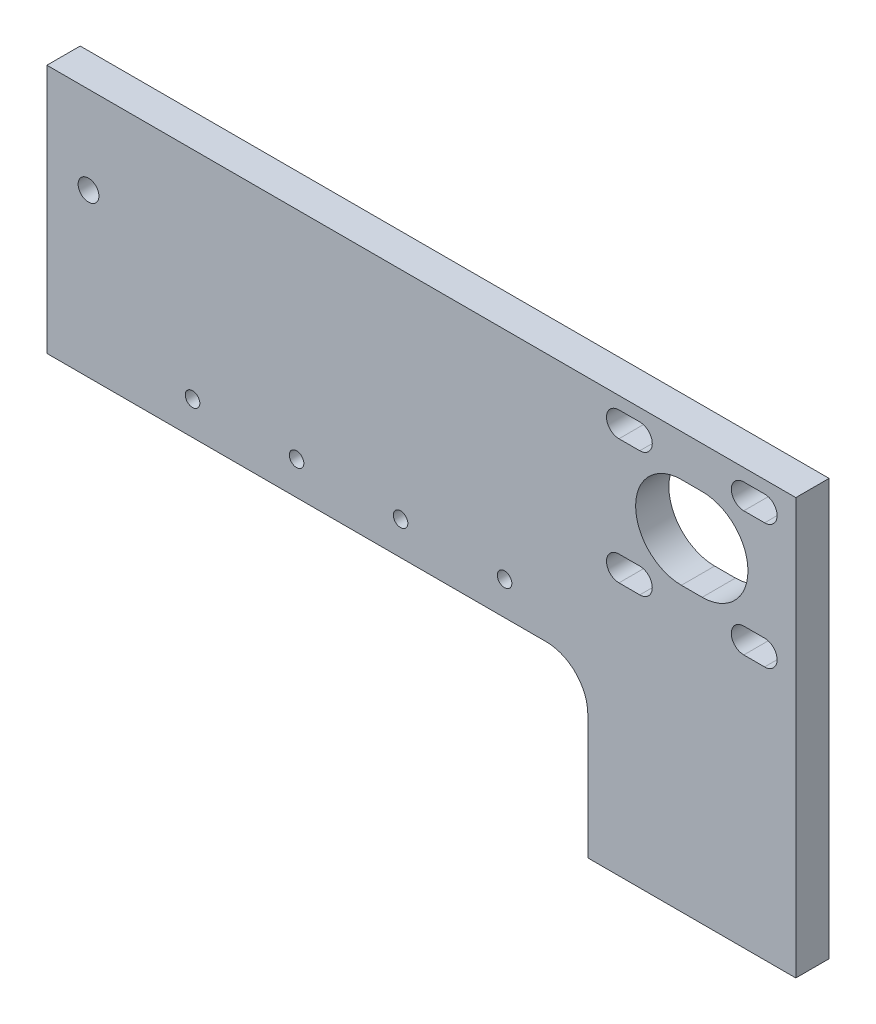
SolidWorks part; units mm, degrees
ref_plane "Front Plane" through (0, 0, 0) normal (0, 0, 1) x (1, 0, 0)
ref_plane "Top Plane" through (0, 0, 0) normal (0, 1, 0) x (1, 0, 0)
ref_plane "Right Plane" through (0, 0, 0) normal (1, 0, 0) x (0, 0, -1)
sketch "Sketch1" plane through (0, 0, 0) normal (0, 0, 1) x (1, 0, 0)
  line L6 (-180, 100) -> (0, 100)
  line L7 (0, 100) -> (0, 0)
  line L8 (0, 0) -> (-50, 0)
  line L9 (-50, 0) -> (-50, 30)
  line L10 (-60, 40) -> (-180, 40)
  line L11 (-180, 40) -> (-180, 100)
  arc A1 (-50, 30) -> (-60, 40) centre (-60, 30) ccw
  point P0 (0, 0)
  dimension "D9" = 10
  dimension "D6" = 180
  dimension "D7" = 100
  dimension "D8" = 60
  dimension "D10" = 50
extrude "BODY" add sketch "Sketch1" along normal blind 8
sketch "Sketch4" plane through (-127.5943, -66.5059, 8) normal (0, 0, 1) x (1, 0, 0)
  line L3 (85.0943, 160.5059) -> (90.0943, 160.5059) construction
  line L4 (85.0943, 163.5059) -> (90.0943, 163.5059)
  line L5 (85.0943, 157.5059) -> (90.0943, 157.5059)
  line L6 (127.5943, 66.5059) -> (127.5943, 166.5059) construction
  line L8 (127.5943, 166.5059) -> (-52.4057, 166.5059) construction
  arc A2 (85.0943, 163.5059) -> (85.0943, 157.5059) centre (85.0943, 160.5059) ccw
  arc A3 (90.0943, 157.5059) -> (90.0943, 163.5059) centre (90.0943, 160.5059) ccw
  point P2 (0, 0)
  point P5 (87.5943, 160.9453)
  point P7 (87.5943, 160.5059)
  dimension "D1" = 3
  dimension "D3" = 3
  dimension "D2" = 40
  dimension "D4" = 5
extrude "Cut-Extrude1" cut sketch "Sketch4" against normal blind 10
pattern_linear "LPattern1" count 2 spacing 30 along (0, -1, 0) count 2 spacing 30 along (1, 0, 0) of "Cut-Extrude1"
sketch "Sketch6" plane through (-127.5943, -66.5059, 8) normal (0, 0, 1) x (1, 0, 0)
  line L0 (87.5943, 163.5059) -> (117.5943, 163.5059) construction
  line L3 (90.0943, 163.5059) -> (85.0943, 163.5059) construction
  line L4 (100.0943, 145.5059) -> (105.0943, 145.5059) construction
  line L5 (120.0943, 163.5059) -> (115.0943, 163.5059) construction
  line L6 (100.0943, 156.5059) -> (105.0943, 156.5059)
  line L7 (100.0943, 134.5059) -> (105.0943, 134.5059)
  line L8 (87.5943, 133.5059) -> (117.5943, 133.5059) construction
  line L9 (90.0943, 133.5059) -> (85.0943, 133.5059) construction
  line L10 (120.0943, 133.5059) -> (115.0943, 133.5059) construction
  line L11 (87.5943, 157.5059) -> (87.5943, 133.5059) construction
  line L12 (85.0943, 157.5059) -> (90.0943, 157.5059) construction
  arc A2 (100.0943, 156.5059) -> (100.0943, 134.5059) centre (100.0943, 145.5059) ccw
  arc A3 (105.0943, 134.5059) -> (105.0943, 156.5059) centre (105.0943, 145.5059) ccw
  point P10 (102.5943, 145.5059)
  point P15 (0, 0)
  point P20 (102.5943, 133.5059)
  point P21 (87.5943, 145.5059)
  dimension "D3" = 11
  dimension "D4" = 5
extrude "Cut-Extrude2" cut sketch "Sketch6" against normal through all
sketch "Sketch7" plane through (0, 0, 8) normal (0, 0, 1) x (1, 0, 0)
  line L0 (-180, 40) -> (-60, 40) construction
  line L3 (0, 0) -> (0, 100) construction
  circle A0 centre (-70, 48) radius 1.75
  point P8 (0, 0)
  point P9 (-75.1534, 75)
  point P10 (0, 0)
  point P11 (-72.8747, 75)
  dimension "D1" = 3.5
  dimension "D2" = 8
  dimension "D3" = 70
extrude "Cut-Extrude3" cut sketch "Sketch7" against normal through all
pattern_linear "LPattern2" count 4 spacing 25 along (-1, 0, 0) of "Cut-Extrude3"
sketch "Sketch8" plane through (0, 0, 8) normal (0, 0, 1) x (1, 0, 0)
  line L0 (-38.5, 79) -> (-197.7512, 79) construction
  line L1 (-180, 100) -> (-180, 40) construction
  arc A0 (-27.5, 90) -> (-27.5, 68) centre (-27.5, 79) ccw construction
  circle A1 centre (-170, 79) radius 2.5
  point P8 (0, 0)
  dimension "D1" = 5
  dimension "D2" = 10
extrude "Cut-Extrude4" cut sketch "Sketch8" against normal through all
